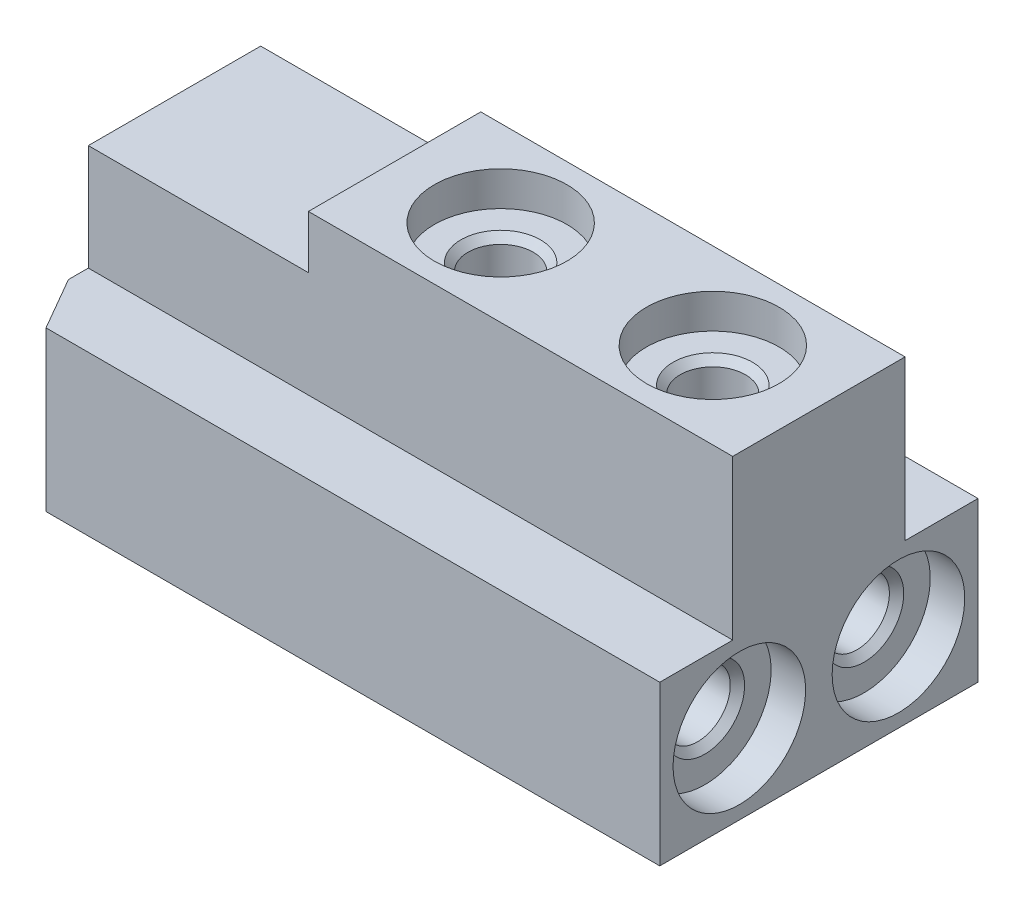
SolidWorks part; units mm, degrees
ref_plane "Front Plane" through (0, 0, 0) normal (0, 0, 1) x (1, 0, 0)
ref_plane "Top Plane" through (0, 0, 0) normal (0, 1, 0) x (1, 0, 0)
ref_plane "Right Plane" through (0, 0, 0) normal (1, 0, 0) x (0, 0, -1)
sketch "Sketch1" plane through (0, 0, 0) normal (1, 0, 0) x (0, 0, -1)
  line L0 (-6, 6) -> (-6, 0)
  line L1 (-6, 0) -> (6, 0)
  line L2 (6, 0) -> (6, 6)
  line L3 (6, 6) -> (3.25, 6)
  line L4 (3.25, 6) -> (3.25, 12)
  line L5 (3.25, 12) -> (-3.25, 12)
  line L6 (-3.25, 12) -> (-3.25, 6)
  line L7 (-3.25, 6) -> (-6, 6)
extrude "Boss-Extrude1" add sketch "Sketch1" along normal blind 24.3
sketch "Sketch2" plane through (0, 0, 0) normal (1, 0, 0) x (0, 0, -1)
  line L0 (-6, 10) -> (6, 10)
  line L1 (6, 10) -> (6, 12)
  line L2 (6, 12) -> (-6, 12)
  line L3 (-6, 12) -> (-6, 10)
extrude "Cut-Extrude1" cut sketch "Sketch2" along normal blind 8.3
ref_plane "Plane1" through (0, 3, 0) normal (0, 1, 0) x (1, 0, 0)
sketch "Sketch3" plane through (0, 3, 0) normal (0, 1, 0) x (1, 0, 0)
  line L0 (15.1401, 3) -> (15.85, 4.2295)
  line L1 (15.85, 4.2295) -> (22.7295, 4.2295)
  line L2 (22.7295, 4.2295) -> (23, 4.5)
  line L3 (23, 4.5) -> (23, 5.5)
  line L4 (23, 5.5) -> (24.3, 5.5)
  line L5 (24.3, 5.5) -> (24.3, 3)
  line L6 (24.3, 3) -> (15.1401, 3)
  line L7 (24.3, 3) -> (15.1401, 3) construction
revolve "Cut-Revolve1" cut sketch "Sketch3" angle 360 about L7 reverse direction yes
cosmetic thread "Cosmetic Thread1" parameters "D1"=6, "D2"=3
sketch "Sketch4" plane through (0, 3, 0) normal (0, 1, 0) x (1, 0, 0)
  line L0 (15.1401, -3) -> (15.85, -1.7705)
  line L1 (15.85, -1.7705) -> (22.7295, -1.7705)
  line L2 (22.7295, -1.7705) -> (23, -1.5)
  line L3 (23, -1.5) -> (23, -0.5)
  line L4 (23, -0.5) -> (24.3, -0.5)
  line L5 (24.3, -0.5) -> (24.3, -3)
  line L6 (24.3, -3) -> (15.1401, -3)
  line L7 (24.3, -3) -> (15.1401, -3) construction
revolve "Cut-Revolve2" cut sketch "Sketch4" angle 360 about L7 reverse direction yes
cosmetic thread "Cosmetic Thread2" parameters "D1"=6, "D2"=3
sketch "Sketch5" plane through (0, 0, 0) normal (0, 0, 1) x (1, 0, 0)
  line L0 (20.3, 12) -> (22.8, 12)
  line L1 (22.8, 12) -> (22.8, 10.7)
  line L2 (22.8, 10.7) -> (21.8, 10.7)
  line L3 (21.8, 10.7) -> (21.5295, 10.4295)
  line L4 (21.5295, 10.4295) -> (21.5295, 3.55)
  line L5 (21.5295, 3.55) -> (20.3, 2.8401)
  line L6 (20.3, 2.8401) -> (20.3, 12)
  line L7 (20.3, 2.8401) -> (20.3, 12) construction
revolve "Cut-Revolve3" cut sketch "Sketch5" angle 360 about L7 reverse direction yes
cosmetic thread "Cosmetic Thread3" parameters "D1"=5.5, "D2"=3
sketch "Sketch6" plane through (0, 0, 0) normal (0, 0, 1) x (1, 0, 0)
  line L0 (12.3, 12) -> (14.8, 12)
  line L1 (14.8, 12) -> (14.8, 10.7)
  line L2 (14.8, 10.7) -> (13.8, 10.7)
  line L3 (13.8, 10.7) -> (13.5295, 10.4295)
  line L4 (13.5295, 10.4295) -> (13.5295, 3.55)
  line L5 (13.5295, 3.55) -> (12.3, 2.8401)
  line L6 (12.3, 2.8401) -> (12.3, 12)
  line L7 (12.3, 2.8401) -> (12.3, 12) construction
revolve "Cut-Revolve4" cut sketch "Sketch6" angle 360 about L7 reverse direction yes
cosmetic thread "Cosmetic Thread4" parameters "D1"=5.5, "D2"=3
sketch "Sketch7" plane through (0, 0, 0) normal (0, 1, 0) x (1, 0, 0)
  line L0 (-1, -7) -> (11.15, -7)
  line L1 (11.15, -7) -> (11.15, -6)
  line L2 (11.15, -6) -> (1.1547, -6)
  line L3 (1.1547, -6) -> (0, -4)
  line L4 (0, -4) -> (0, 4)
  line L5 (0, 4) -> (1.1547, 6)
  line L6 (1.1547, 6) -> (11.15, 6)
  line L7 (11.15, 6) -> (11.15, 7)
  line L8 (11.15, 7) -> (-1, 7)
  line L9 (-1, 7) -> (-1, -7)
extrude "Cut-Extrude2" cut sketch "Sketch7" along normal blind 6
ref_plane "Plane2" through (24.3, 0, 0) normal (1, 0, 0) x (0, 0, -1)
ref_plane "TO_ZYL XY" through (24.3, 0, 0) normal (1, 0, 0) x (0, 0, -1)
ref_plane "TO_ZYL XZ" through (0, 0, 0) normal (0, -1, 0) x (-1, 0, 0)
ref_plane "TO_ZYL YZ" through (0, 0, 0) normal (0, 0, -1) x (-1, 0, 0)
ref_axis "TO_ZYL X" through (24.3, 0, 80.9) along (0, 0, -1)
ref_axis "TO_ZYL Y" through (24.3, -50, 0) along (0, 1, 0)
ref_axis "TO_ZYL Z" through (80.9, 0, 0) along (-1, 0, 0)
sketch3d "TO_ZYL"
  point P0 (24.3, 0, 0)
other "Freeze***"
